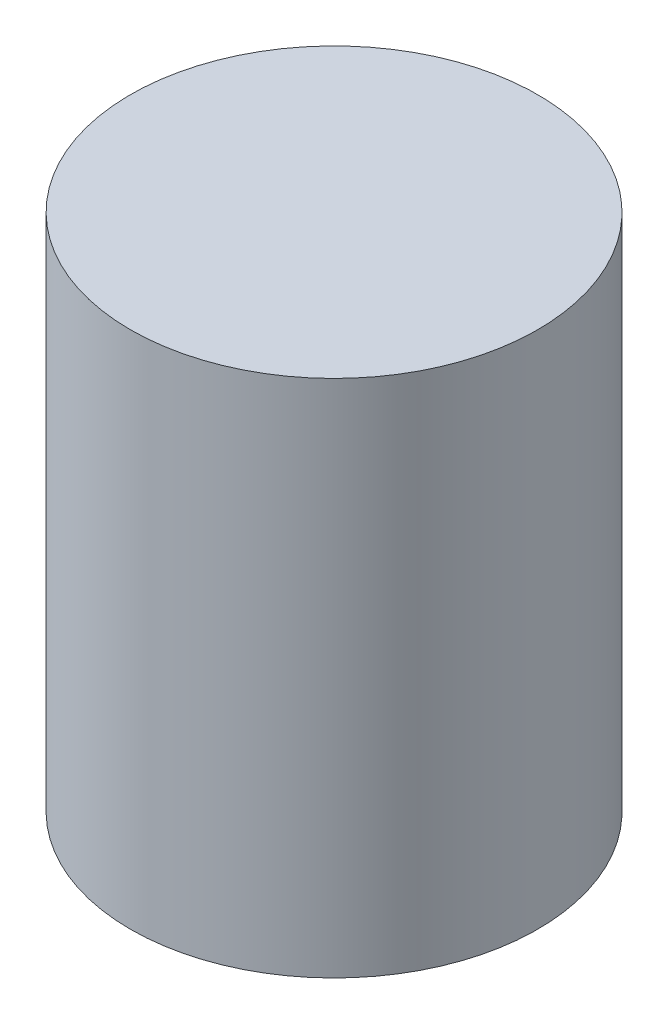
SolidWorks part; units mm, degrees
ref_plane "Front Plane" through (0, 0, 0) normal (0, 0, 1) x (1, 0, 0)
ref_plane "Top Plane" through (0, 0, 0) normal (0, 1, 0) x (1, 0, 0)
ref_plane "Right Plane" through (0, 0, 0) normal (1, 0, 0) x (0, 0, -1)
sketch "Sketch1" plane through (0, 0, 0) normal (0, 1, 0) x (1, 0, 0)
  circle A0 centre (0, 0) radius 20
  dimension "D1" = 40
extrude "Boss-Extrude1" add sketch "Sketch1" along normal blind 51
